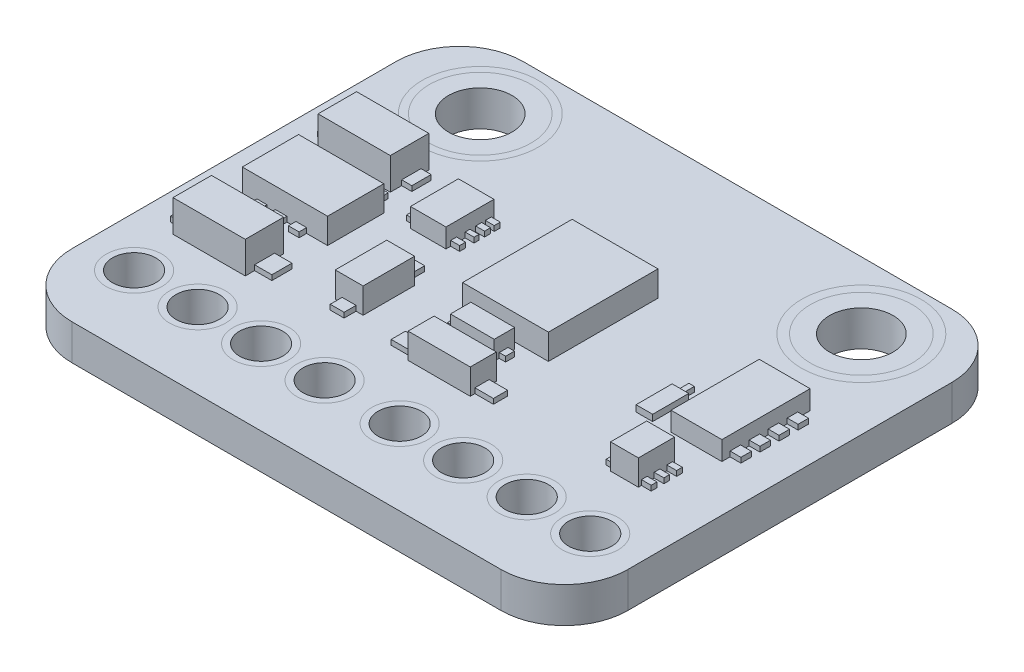
SolidWorks part; units mm, degrees
ref_plane "Front Plane" through (0, 0, 0) normal (0, 0, 1) x (1, 0, 0)
ref_plane "Top Plane" through (0, 0, 0) normal (0, 1, 0) x (1, 0, 0)
ref_plane "Right Plane" through (0, 0, 0) normal (1, 0, 0) x (0, 0, -1)
sketch "Sketch1" plane through (0, 0, 0) normal (0, 1, 0) x (1, 0, 0)
  line L1 (8.5725, -9.017) -> (-8.5725, -9.017)
  line L2 (11.1125, -6.477) -> (11.1125, 6.477)
  line L3 (8.5725, 9.017) -> (-8.5725, 9.017)
  line L4 (-11.1125, -6.477) -> (-11.1125, 6.477)
  line L5 (11.1125, -9.017) -> (-11.1125, 9.017) construction
  line L6 (11.1125, 9.017) -> (-11.1125, -9.017) construction
  arc A0 (8.5725, -9.017) -> (11.1125, -6.477) centre (8.5725, -6.477) ccw
  arc A1 (11.1125, 6.477) -> (8.5725, 9.017) centre (8.5725, 6.477) ccw
  arc A2 (-8.5725, 9.017) -> (-11.1125, 6.477) centre (-8.5725, 6.477) ccw
  arc A3 (-8.5725, -9.017) -> (-11.1125, -6.477) centre (-8.5725, -6.477) cw
  point P0 (0, 0)
  dimension "D3" = 2.54
  dimension "D1" = 18.034
  dimension "D2" = 22.225
extrude "Boss-Extrude1" add sketch "Sketch1" along normal blind 1.4224
sketch "Sketch2" plane through (0, 1.4224, 0) normal (0, 1, 0) x (1, 0, 0)
  line L0 (0, 9.017) -> (0, -9.017) construction
  line L1 (8.5725, 9.017) -> (-8.5725, 9.017) construction
  line L2 (-8.5725, -9.017) -> (8.5725, -9.017) construction
  line L3 (-6.35, 6.35) -> (6.35, 6.35) construction
  line L4 (-7.62, 7.62) -> (-7.62, 9.017) construction
  line L5 (-0.635, -5.9926) -> (0.635, -5.9926) construction
  line L6 (-1.5004, -6.858) -> (-1.5004, -9.017) construction
  line L7 (1.5004, -6.858) -> (1.5004, -9.017) construction
  line L8 (7.62, 7.62) -> (7.62, 9.017) construction
  circle A0 centre (-7.62, 6.35) radius 1.27
  circle A1 centre (-1.5004, -5.9926) radius 0.8654
  circle A2 centre (-4.0404, -5.9926) radius 0.8654
  circle A3 centre (-6.5804, -5.9926) radius 0.8654
  circle A4 centre (-9.1204, -5.9926) radius 0.8654
  circle A5 centre (9.1204, -5.9926) radius 0.8654
  circle A6 centre (6.5804, -5.9926) radius 0.8654
  circle A7 centre (4.0404, -5.9926) radius 0.8654
  circle A8 centre (1.5004, -5.9926) radius 0.8654
  circle A9 centre (7.62, 6.35) radius 1.27
  point P27 (0, -5.9926)
  point P30 (0, 6.35)
  dimension "D2" = 2.54
  dimension "D1" = 6.35
  dimension "D3" = 1.397
  dimension "D4" = 0.635
  dimension "D5" = 2.159
  dimension "D6" = 4
extrude "Cut-Extrude1" cut sketch "Sketch2" against normal blind 6.5024
sketch "Sketch3" plane through (0, 1.4224, 0) normal (0, 1, 0) x (1, 0, 0)
  circle A0 centre (-7.62, 6.35) radius 2.032
  circle A1 centre (-1.5004, -5.9926) radius 0.8654
  circle A2 centre (-1.5004, -5.9926) radius 0.8654 construction
  circle A3 centre (-7.62, 6.35) radius 1.27
  circle A4 centre (-7.62, 6.35) radius 1.27 construction
  circle A5 centre (9.1204, -5.9926) radius 0.8654
  circle A6 centre (9.1204, -5.9926) radius 0.8654 construction
  circle A7 centre (-9.1204, -5.9926) radius 0.8654
  circle A8 centre (-9.1204, -5.9926) radius 0.8654 construction
  circle A9 centre (-6.5804, -5.9926) radius 0.8654
  circle A10 centre (-6.5804, -5.9926) radius 0.8654 construction
  circle A11 centre (-4.0404, -5.9926) radius 0.8654
  circle A12 centre (-4.0404, -5.9926) radius 0.8654 construction
  circle A13 centre (7.62, 6.35) radius 1.27
  circle A14 centre (7.62, 6.35) radius 1.27 construction
  circle A15 centre (1.5004, -5.9926) radius 0.8654
  circle A16 centre (1.5004, -5.9926) radius 0.8654 construction
  circle A17 centre (4.0404, -5.9926) radius 0.8654
  circle A18 centre (4.0404, -5.9926) radius 0.8654 construction
  circle A19 centre (6.5804, -5.9926) radius 0.8654
  circle A20 centre (6.5804, -5.9926) radius 0.8654 construction
  circle A21 centre (7.62, 6.35) radius 2.032
  circle A22 centre (-1.5004, -5.9926) radius 1.1194
  circle A23 centre (9.1204, -5.9926) radius 1.1194
  circle A24 centre (-9.1204, -5.9926) radius 1.1194
  circle A25 centre (-6.5804, -5.9926) radius 1.1194
  circle A26 centre (-4.0404, -5.9926) radius 1.1194
  circle A27 centre (1.5004, -5.9926) radius 1.1194
  circle A28 centre (4.0404, -5.9926) radius 1.1194
  circle A29 centre (6.5804, -5.9926) radius 1.1194
  dimension "D1" = 0
  dimension "D2" = 0
  dimension "D3" = 0
  dimension "D4" = 0
  dimension "D5" = 0
  dimension "D6" = 0
  dimension "D7" = 0
  dimension "D8" = 0
  dimension "D9" = 0
  dimension "D10" = 0
  dimension "D11" = 0.762
  dimension "D12" = 0.254
split line "Split Line1"
sketch "Sketch4" plane through (0, 1.4224, 0) normal (0, 1, 0) x (1, 0, 0)
  line L1 (-9.5895, 3.3741) -> (-6.7008, 3.3741)
  line L2 (-9.5895, 3.3741) -> (-9.5895, 1.835)
  line L3 (-9.5895, 1.835) -> (-6.7008, 1.835)
  line L4 (-6.7008, 3.3741) -> (-6.7008, 1.835)
  line L5 (-9.5185, 0.9826) -> (-6.1089, 0.9826)
  line L6 (-9.5185, 0.9826) -> (-9.5185, -1.2668)
  line L7 (-9.5185, -1.2668) -> (-6.1089, -1.2668)
  line L8 (-6.1089, 0.9826) -> (-6.1089, -1.2668)
  line L9 (-9.5895, -2.427) -> (-6.7008, -2.427)
  line L10 (-9.5895, -2.427) -> (-9.5895, -3.966)
  line L11 (-9.5895, -3.966) -> (-6.7008, -3.966)
  line L12 (-6.7008, -2.427) -> (-6.7008, -3.966)
  line L13 (-5.0434, 2.9005) -> (-3.6227, 2.9005)
  line L14 (-5.0434, 2.9005) -> (-5.0434, 0.9826)
  line L15 (-5.0434, 0.9826) -> (-3.6227, 0.9826)
  line L16 (-3.6227, 2.9005) -> (-3.6227, 0.9826)
  line L17 (-4.0963, -0.9116) -> (-2.9834, -0.9116)
  line L18 (-4.0963, -0.9116) -> (-4.0963, -2.9716)
  line L19 (-4.0963, -2.9716) -> (-2.9834, -2.9716)
  line L20 (-2.9834, -0.9116) -> (-2.9834, -2.9716)
  line L21 (-0.5209, -3.6346) -> (1.9653, -3.6346)
  line L22 (-0.5209, -3.6346) -> (-0.5209, -2.5927)
  line L23 (-0.5209, -2.5927) -> (1.9653, -2.5927)
  line L24 (1.9653, -3.6346) -> (1.9653, -2.5927)
  line L25 (-0.5209, -1.9416) -> (1.2312, -1.9416)
  line L26 (-0.5209, -1.9416) -> (-0.5209, -1.1247)
  line L27 (-0.5209, -1.1247) -> (1.2312, -1.1247)
  line L28 (1.2312, -1.9416) -> (1.2312, -1.1247)
  line L29 (-1.1129, -0.8642) -> (2.3204, -0.8642)
  line L30 (-1.1129, -0.8642) -> (-1.1129, 3.5162)
  line L31 (-1.1129, 3.5162) -> (2.3204, 3.5162)
  line L32 (2.3204, -0.8642) -> (2.3204, 3.5162)
  line L33 (7.2218, 2.6638) -> (9.258, 2.6638)
  line L34 (7.2218, 2.6638) -> (7.2218, -0.8642)
  line L35 (7.2218, -0.8642) -> (9.258, -0.8642)
  line L36 (9.258, 2.6638) -> (9.258, -0.8642)
  line L37 (5.8248, -0.8642) -> (6.4877, -0.8642)
  line L38 (5.8248, -0.8642) -> (5.8248, 0.5801)
  line L39 (5.8248, 0.5801) -> (6.4877, 0.5801)
  line L40 (6.4877, -0.8642) -> (6.4877, 0.5801)
  line L41 (7.3638, -1.9771) -> (8.4767, -1.9771)
  line L42 (7.3638, -1.9771) -> (7.3638, -3.4215)
  line L43 (7.3638, -3.4215) -> (8.4767, -3.4215)
  line L44 (8.4767, -1.9771) -> (8.4767, -3.4215)
  point P44 (8.4767, -1.9771)
extrude "Boss-Extrude2" add sketch "Sketch4" along normal blind 1.27 contours L3 L4 L1 L2 | L9 L12 L11 L10
extrude "Boss-Extrude3" add sketch "Sketch4<3>" along normal blind 1.016 contours L8 L7 L6 L5 | L29 L32 L31 L30 | L20 L19 L18 L17 | L21 L24 L23 L22 | L43 L44 L41 L42
sketch "Sketch4<3>" plane through (0, 1.4224, 0) normal (0, 1, 0) x (1, 0, 0) same geometry as "Sketch4"
extrude "Boss-Extrude4" add sketch "Sketch4<4>" along normal blind 0.762 contours L15 L16 L13 L14 | L34 L35 L36 L33 | L27 L28 L25 L26
sketch "Sketch4<4>" plane through (0, 1.4224, 0) normal (0, 1, 0) x (1, 0, 0) same geometry as "Sketch4"
extrude "Boss-Extrude5" add sketch "Sketch4<5>" along normal blind 0.254 contours L37 L40 L39 L38
sketch "Sketch4<5>" plane through (0, 1.4224, 0) normal (0, 1, 0) x (1, 0, 0) same geometry as "Sketch4"
sketch "Sketch5" plane through (0, 1.4224, 0) normal (0, 1, 0) x (1, 0, 0)
  line L0 (6.9566, 0.6437) -> (9.6915, 0.6437)
  line L1 (6.9566, -0.538) -> (9.6915, -0.538)
  line L2 (6.9566, -0.538) -> (6.9566, -0.1183)
  line L3 (6.9566, -0.1183) -> (9.6915, -0.1183)
  line L4 (9.6915, -0.538) -> (9.6915, -0.1183)
  line L5 (6.9566, 0.224) -> (6.9566, 0.6437)
  line L6 (6.9566, 0.224) -> (9.6915, 0.224)
  line L7 (9.6915, 0.224) -> (9.6915, 0.6437)
  line L8 (6.9566, 1.4057) -> (9.6915, 1.4057)
  line L9 (6.9566, 0.986) -> (6.9566, 1.4057)
  line L10 (6.9566, 0.986) -> (9.6915, 0.986)
  line L11 (9.6915, 0.986) -> (9.6915, 1.4057)
  line L12 (6.9566, 2.1677) -> (9.6915, 2.1677)
  line L13 (6.9566, 1.748) -> (6.9566, 2.1677)
  line L14 (6.9566, 1.748) -> (9.6915, 1.748)
  line L15 (9.6915, 1.748) -> (9.6915, 2.1677)
  line L16 (7.065, -2.7919) -> (8.8656, -2.7919)
  line L17 (7.065, -3.2999) -> (8.8656, -3.2999)
  line L18 (7.065, -3.2999) -> (7.065, -3.0697)
  line L19 (7.065, -3.0697) -> (8.8656, -3.0697)
  line L20 (8.8656, -3.2999) -> (8.8656, -3.0697)
  line L21 (7.065, -2.7919) -> (7.065, -2.5617)
  line L22 (7.065, -2.5617) -> (8.8656, -2.5617)
  line L23 (8.8656, -2.7919) -> (8.8656, -2.5617)
  line L24 (7.065, -2.2839) -> (8.8656, -2.2839)
  line L25 (7.065, -2.2839) -> (7.065, -2.0537)
  line L26 (7.065, -2.0537) -> (8.8656, -2.0537)
  line L27 (8.8656, -2.2839) -> (8.8656, -2.0537)
  line L29 (-0.8416, -1.3909) -> (1.487, -1.3909)
  line L30 (-0.8416, -1.3909) -> (-0.8416, -1.7429)
  line L31 (-0.8416, -1.7429) -> (1.487, -1.7429)
  line L32 (1.487, -1.3909) -> (1.487, -1.7429)
  line L33 (-1.3832, -2.8802) -> (2.7055, -2.8802)
  line L34 (-1.3832, -2.8802) -> (-1.3832, -3.4488)
  line L35 (-1.3832, -3.4488) -> (2.7055, -3.4488)
  line L36 (2.7055, -2.8802) -> (2.7055, -3.4488)
  line L37 (-3.8202, -3.4488) -> (-3.2651, -3.4488)
  line L38 (-3.8202, -3.4488) -> (-3.8202, -0.2266)
  line L39 (-3.8202, -0.2266) -> (-3.2651, -0.2266)
  line L40 (-3.2651, -3.4488) -> (-3.2651, -0.2266)
  line L41 (-10.0699, -2.7919) -> (-6.0085, -2.7919)
  line L42 (-10.0699, -2.7919) -> (-10.0699, -3.5948)
  line L43 (-10.0699, -3.5948) -> (-6.0085, -3.5948)
  line L44 (-6.0085, -2.7919) -> (-6.0085, -3.5948)
  line L45 (-8.9324, -0.7091) -> (-8.5327, -0.7091)
  line L46 (-8.9324, -0.7091) -> (-8.9324, -1.5669)
  line L47 (-8.9324, -1.5669) -> (-8.5327, -1.5669)
  line L48 (-8.5327, -0.7091) -> (-8.5327, -1.5669)
  line L49 (-8.1996, -0.7091) -> (-7.7333, -0.7091)
  line L50 (-8.1996, -0.7091) -> (-8.1996, -1.5669)
  line L51 (-8.1996, -1.5669) -> (-7.7333, -1.5669)
  line L52 (-7.7333, -0.7091) -> (-7.7333, -1.5669)
  line L53 (-7.3736, -0.7091) -> (-6.9472, -0.7091)
  line L54 (-7.3736, -0.7091) -> (-7.3736, -1.5669)
  line L55 (-7.3736, -1.5669) -> (-6.9472, -1.5669)
  line L56 (-6.9472, -0.7091) -> (-6.9472, -1.5669)
  line L57 (-9.0523, 0.4634) -> (-8.7325, 0.4634)
  line L58 (-9.0523, 0.4634) -> (-9.0523, 1.5692)
  line L59 (-9.0523, 1.5692) -> (-8.7325, 1.5692)
  line L60 (-8.7325, 0.4634) -> (-8.7325, 1.5692)
  line L61 (-6.9472, 0.4634) -> (-6.5209, 0.4634)
  line L62 (-6.9472, 0.4634) -> (-6.9472, 1.5692)
  line L63 (-6.9472, 1.5692) -> (-6.5209, 1.5692)
  line L64 (-6.5209, 0.4634) -> (-6.5209, 1.5692)
  line L65 (-10.0699, 3.0614) -> (-6.2944, 3.0614)
  line L66 (-10.0699, 3.0614) -> (-10.0699, 2.2887)
  line L67 (-10.0699, 2.2887) -> (-6.2944, 2.2887)
  line L68 (-6.2944, 3.0614) -> (-6.2944, 2.2887)
  line L69 (-5.3884, 2.7949) -> (-3.2651, 2.7949)
  line L70 (-5.3884, 2.7949) -> (-5.3884, 2.5551)
  line L71 (-5.3884, 2.5551) -> (-3.2651, 2.5551)
  line L72 (-3.2651, 2.7949) -> (-3.2651, 2.5551)
  line L73 (-5.3884, 2.4086) -> (-3.2651, 2.4086)
  line L74 (-5.3884, 2.4086) -> (-5.3884, 2.1677)
  line L75 (-5.3884, 2.1677) -> (-3.2651, 2.1677)
  line L76 (-3.2651, 2.4086) -> (-3.2651, 2.1677)
  line L77 (-5.3884, 1.9422) -> (-3.2651, 1.9422)
  line L78 (-5.3884, 1.9422) -> (-5.3884, 1.748)
  line L79 (-5.3884, 1.748) -> (-3.2651, 1.748)
  line L80 (-3.2651, 1.9422) -> (-3.2651, 1.748)
  line L81 (-5.3884, 1.4057) -> (-3.2651, 1.4057)
  line L82 (-5.3884, 1.4057) -> (-5.3884, 1.1695)
  line L83 (-5.3884, 1.1695) -> (-3.2651, 1.1695)
  line L84 (-3.2651, 1.4057) -> (-3.2651, 1.1695)
  line L85 (6.088, 0.0656) -> (6.3065, 0.0656)
  line L86 (6.088, 0.0656) -> (6.088, 0.986)
  line L87 (6.088, 0.986) -> (6.3065, 0.986)
  line L88 (6.3065, 0.0656) -> (6.3065, 0.986)
  dimension "D1" = 4
  dimension "D2" = 3
extrude "Boss-Extrude6" add sketch "Sketch5" along normal blind 0.2032
sketch "Sketch6" plane through (0, 1.4224, 0) normal (0, 1, 0) x (1, 0, 0)
  circle A0 centre (-7.62, 6.35) radius 2.3193
  circle A1 centre (7.62, 6.35) radius 2.39
split line "Split Line2"
